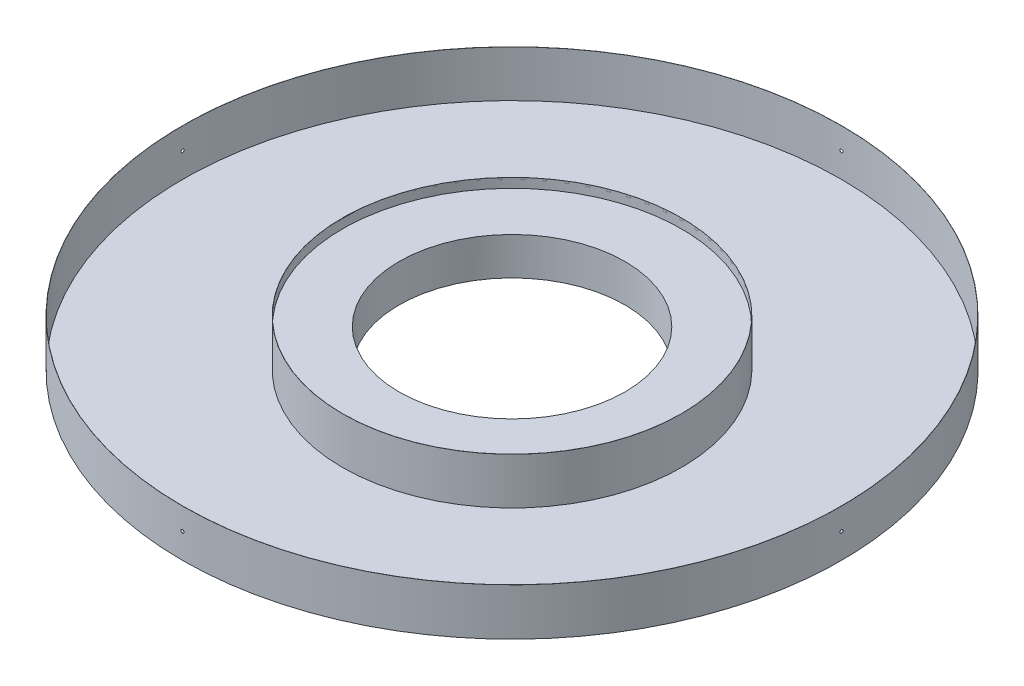
SolidWorks part; units mm, degrees
material "1345 Alloy"
ref_plane "Front Plane" through (0, 0, 0) normal (0, 0, 1) x (1, 0, 0)
ref_plane "Top Plane" through (0, 0, 0) normal (0, 1, 0) x (1, 0, 0)
ref_plane "Right Plane" through (0, 0, 0) normal (1, 0, 0) x (0, 0, -1)
sketch "Sketch1" plane through (0, 0, 0) normal (0, 1, 0) x (1, 0, 0)
  circle A0 centre (0, 0) radius 1750
extrude "Boss-Extrude1" add sketch "Sketch1" along normal blind 500
sketch "Sketch2" plane through (0, 500, 0) normal (0, 1, 0) x (1, 0, 0)
  circle A0 centre (0, 0) radius 900
extrude "Cut-Extrude2" cut sketch "Sketch2" against normal blind 300
sketch "Sketch3" plane through (0, 0, 0) normal (0, -1, 0) x (1, 0, 0)
  circle A0 centre (0, 0) radius 600
extrude "Cut-Extrude3" cut sketch "Sketch3" against normal blind 300
sketch "Sketch4" plane through (0, 500, 0) normal (0, 1, 0) x (1, 0, 0)
  circle A0 centre (0, 0) radius 1749.25
  circle A1 centre (0, 0) radius 900.75
extrude "Cut-Extrude4" cut sketch "Sketch4" against normal blind 497
sketch "Sketch6" plane through (0, 0, 0) normal (1, 0, 0) x (0, 0, -1)
  line L0 (0, 0) -> (0, 250)
  line L1 (0, 250) -> (1750, 250)
  line L2 (1750, 0) -> (1750, 500) construction
  line L3 (1750, 250) -> (1750, 0)
  line L4 (1750, 0) -> (-1750, 0)
  line L5 (-1750, 0) -> (-1750, 250)
  line L6 (-1750, 500) -> (-1750, 0) construction
  line L7 (-1750, 250) -> (0, 250)
  line L8 (1750, 250) -> (1750, 500)
  line L9 (1750, 500) -> (-1750, 500)
  line L10 (-1750, 500) -> (-1750, 250)
extrude "Cut-Extrude5" cut sketch "Sketch6" against normal through all both and the other way through all contours L9 L10 L7 L1 L8 region at (0, 375, 0)
ref_plane "Plane1" through (0, 0, 2000) normal (0, 0, 1) x (1, 0, 0)
sketch "Sketch7" plane through (0, 0, 2000) normal (0, 0, 1) x (1, 0, 0)
  circle A0 centre (0, 133.8976) radius 8.382
extrude "Cut-Extrude6" cut sketch "Sketch7" against normal blind 500
pattern_circular "CirPattern1" count 4 every 90 about axis through (0, 500, 0) along (0, -1, 0) of "Cut-Extrude6" reverse direction yes
ref_plane "Plane2" through (-1237.4369, 0, 1237.4369) normal (-0.7071, 0, 0.7071) x (0, -1, 0)
sketch "Sketch8" plane through (-1237.4369, 0, 1237.4369) normal (-0.7071, 0, 0.7071) x (0, -1, 0)
  line L7 (-147.4283, -15.9472) -> (-124.8755, -38.5)
  line L8 (-124.8755, -38.5) -> (-92.9811, -38.5)
  line L9 (-92.9811, -38.5) -> (-70.4283, -15.9472)
  line L10 (-70.4283, -15.9472) -> (-70.4283, 15.9472)
  line L11 (-70.4283, 15.9472) -> (-92.9811, 38.5)
  line L12 (-92.9811, 38.5) -> (-124.8755, 38.5)
  line L13 (-124.8755, 38.5) -> (-147.4283, 15.9472)
  line L14 (-147.4283, 15.9472) -> (-147.4283, -15.9472)
  circle A0 centre (-108.9283, 0) radius 38.5 construction
extrude "Cut-Extrude8" cut sketch "Sketch8" against normal blind 10
